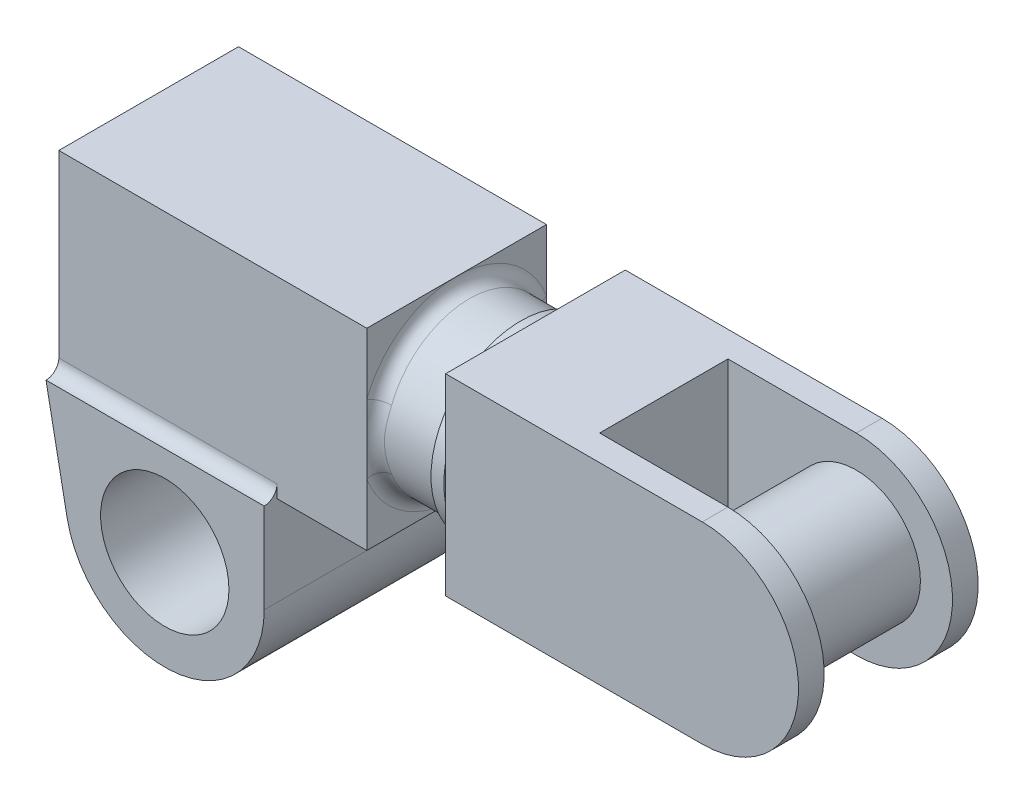
SolidWorks part; units mm, degrees
ref_plane "Front Plane" through (0, 0, 0) normal (0, 0, 1) x (1, 0, 0)
ref_plane "Top Plane" through (0, 0, 0) normal (0, 1, 0) x (1, 0, 0)
ref_plane "Right Plane" through (0, 0, 0) normal (1, 0, 0) x (0, 0, -1)
sketch "Sketch1" plane through (0, 0, 0) normal (1, 0, 0) x (0, 0, -1)
  line L1 (-70, 75) -> (70, 75)
  line L2 (-70, 75) -> (-70, -75)
  line L3 (-70, -75) -> (70, -75)
  line L4 (70, 75) -> (70, -75)
  line L5 (-70, 75) -> (70, -75) construction
  line L6 (-70, -75) -> (70, 75) construction
  point P0 (0, 0)
  dimension "D1" = 150
  dimension "D2" = 140
extrude "Boss-Extrude1" add sketch "Sketch1" along normal blind 240
sketch "Sketch2" plane through (240, 0, 0) normal (1, 0, 0) x (0, 0, -1)
  circle A0 centre (0, 0) radius 65
  dimension "D1" = 130
extrude "Boss-Extrude2" add sketch "Sketch2" along normal blind 50
sketch "Sketch3" plane through (290, 0, 0) normal (1, 0, 0) x (0, 0, -1)
  circle A0 centre (0, 0) radius 70
  dimension "D1" = 140
extrude "Boss-Extrude3" add sketch "Sketch3" along normal blind 10
sketch "Sketch4" plane through (0, 0, 0) normal (0, 0, 1) x (1, 0, 0)
  line L0 (0, -75) -> (16.5223, -160)
  line L2 (0, 75) -> (0, -75) construction
  line L3 (170.0569, -145) -> (170.0569, -75)
  line L4 (240, -75) -> (0, -75) construction
  line L5 (0, -75) -> (170.0569, -75)
  arc A0 (16.4398, -159.5753) -> (170.0569, -145) centre (92.5569, -145) ccw
  circle A1 centre (92.5569, -145) radius 50
  dimension "D1" = 155
  dimension "D2" = 100
  dimension "D3" = 191
  dimension "D4" = 85
  dimension "D5" = 70
extrude "Boss-Extrude4" add sketch "Sketch4" along normal mid plane 160 contours L0 A0 L3 L5 A1 region at (85.0284, -77.2511, 0)
fillet "Fillet1" radius 10 3 edges at (85.0284, -75, -70) (240, 0, -65) (85.0284, -75, 70)
sketch "Sketch5" plane through (300, 0, 0) normal (1, 0, 0) x (0, 0, -1)
  circle A0 centre (0, 0) radius 65
  dimension "D1" = 130
extrude "Boss-Extrude5" add sketch "Sketch5" along normal blind 20
sketch "Sketch6" plane through (0, 0, 0) normal (0, 0, 1) x (1, 0, 0)
  line L0 (501.4182, 75) -> (301.4182, 75)
  line L1 (301.4182, 75) -> (301.4182, -75)
  line L2 (301.4182, -75) -> (501.4182, -75)
  arc A0 (501.4182, -75) -> (501.4182, 75) centre (501.4182, 0) ccw
  dimension "D1" = 150
  dimension "D2" = 200
extrude "Boss-Extrude6" add sketch "Sketch6" along normal mid plane 140
sketch "Sketch7" plane through (0, 0, 0) normal (0, 0, 1) x (1, 0, 0)
  line L0 (501.4182, 75) -> (401.4182, 75)
  line L1 (501.4182, 75) -> (301.4182, 75) construction
  line L2 (401.4182, 75) -> (401.4182, -75)
  line L3 (301.4182, -75) -> (501.4182, -75) construction
  line L4 (401.4182, -75) -> (501.4182, -75)
  arc A0 (501.4182, -75) -> (501.4182, 75) centre (501.4182, 0) ccw construction
  arc A1 (501.4182, -75) -> (501.4182, 75) centre (501.4182, 0) ccw
extrude "Cut-Extrude1" cut sketch "Sketch7" against normal mid plane 100
sketch "Sketch8" plane through (0, 0, 70) normal (0, 0, 1) x (1, 0, 0)
  circle A0 centre (501.4182, 0) radius 50
  dimension "D1" = 100
extrude "Boss-Extrude8" add sketch "Sketch8" against normal blind 140
